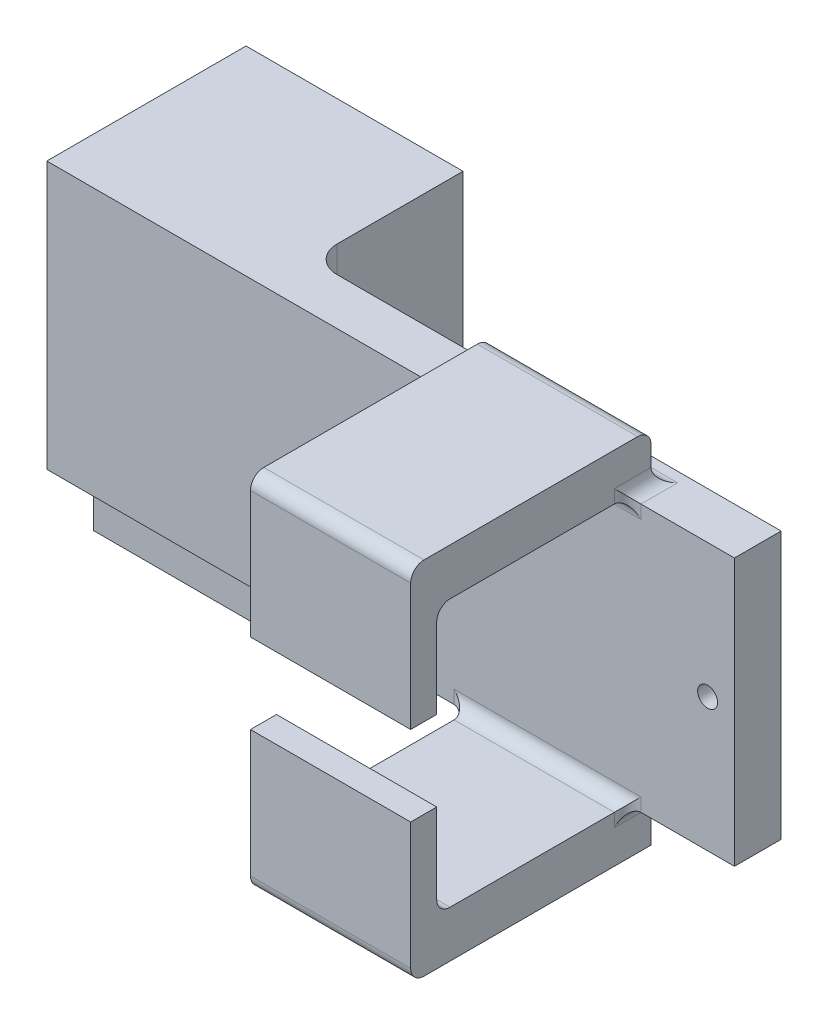
SolidWorks part; units mm, degrees
ref_plane "Front Plane" through (0, 0, 0) normal (0, 0, 1) x (1, 0, 0)
ref_plane "Top Plane" through (0, 0, 0) normal (0, 1, 0) x (1, 0, 0)
ref_plane "Right Plane" through (0, 0, 0) normal (1, 0, 0) x (0, 0, -1)
sketch "Sketch1" plane through (0, 0, 0) normal (0, 0, 1) x (1, 0, 0)
  line L1 (-25.75, 10) -> (25.75, 10)
  line L2 (-25.75, 10) -> (-25.75, -10)
  line L3 (-25.75, -10) -> (25.75, -10)
  line L4 (25.75, 10) -> (25.75, -10)
  line L5 (-25.75, 10) -> (25.75, -10) construction
  line L6 (-25.75, -10) -> (25.75, 10) construction
  point P0 (0, 0)
  dimension "D1" = 51.5
  dimension "D2" = 20
extrude "Boss-Extrude1" add sketch "Sketch1" along normal blind 3.5
sketch "Sketch2" plane through (0, 10, 0) normal (0, 1, 0) x (1, 0, 0)
  line L0 (25.75, -3.5) -> (25.75, 0) construction
  line L1 (17.75, -1.75) -> (5.75, -1.75)
  line L2 (17.75, -1.75) -> (17.75, -19.75)
  line L3 (17.75, -19.75) -> (5.75, -19.75)
  line L4 (5.75, -1.75) -> (5.75, -19.75)
  line L5 (25.75, 0) -> (-25.75, 0) construction
  dimension "D1" = 12
  dimension "D2" = 18
  dimension "D3" = 8
  dimension "D4" = 1.75
extrude "Boss-Extrude2" add sketch "Sketch2" along normal blind 3.5
fillet "Fillet1" radius 1 1 edges at (11.75, 10, 1.75)
fillet "Fillet2" radius 1 1 edges at (11.75, 10, 3.5)
sketch "Sketch3" plane through (0, -10, 0) normal (0, -1, 0) x (-1, 0, 0)
  line L0 (25.75, 0) -> (-25.75, 0) construction
  line L1 (-17.75, -1.75) -> (-5.75, -1.75)
  line L2 (-17.75, -1.75) -> (-17.75, -19.75)
  line L3 (-17.75, -19.75) -> (-5.75, -19.75)
  line L4 (-5.75, -1.75) -> (-5.75, -19.75)
  line L5 (-25.75, -3.5) -> (-25.75, 0) construction
  dimension "D1" = 12
  dimension "D2" = 1.75
  dimension "D3" = 8
  dimension "D4" = 18
extrude "Boss-Extrude3" add sketch "Sketch3" along normal blind 3.5
fillet "Fillet3" radius 1 1 edges at (11.75, -10, 1.75)
fillet "Fillet4" radius 1 1 edges at (11.75, -10, 3.5)
fillet "Fillet5" radius 1 1 edges at (17.75, 10, 2.125)
fillet "Fillet6" radius 1 1 edges at (5.75, 10, 2.125)
fillet "Fillet7" radius 1 1 edges at (17.75, 10, 3.5)
fillet "Fillet8" radius 1 1 edges at (5.75, 10, 3.5)
fillet "Fillet9" radius 1 1 edges at (5.75, -10, 2.125)
fillet "Fillet10" radius 1 1 edges at (5.75, -10, 3.5)
fillet "Fillet11" radius 1 1 edges at (17.75, -10, 2.125)
fillet "Fillet12" radius 1 1 edges at (17.75, -10, 3.5)
sketch "Sketch4" plane through (0, -10, 0) normal (0, 1, 0) x (1, 0, 0)
  line L0 (17.75, -4.5) -> (17.75, -19.75) construction
  line L1 (5.75, -19.75) -> (17.75, -19.75)
  line L2 (5.75, -19.75) -> (5.75, -17.8)
  line L3 (5.75, -17.8) -> (17.75, -17.8)
  line L4 (17.75, -19.75) -> (17.75, -17.8)
  dimension "D1" = 1.95
  dimension "D2" = 12
extrude "Boss-Extrude4" add sketch "Sketch4" along normal blind 7
sketch "Sketch5" plane through (0, 10, 0) normal (0, -1, 0) x (-1, 0, 0)
  line L0 (-17.75, -19.75) -> (-17.75, -4.5) construction
  line L1 (-5.75, -19.75) -> (-17.75, -19.75)
  line L2 (-5.75, -19.75) -> (-5.75, -17.8)
  line L3 (-5.75, -17.8) -> (-17.75, -17.8)
  line L4 (-17.75, -19.75) -> (-17.75, -17.8)
  dimension "D1" = 12
  dimension "D2" = 1.95
extrude "Boss-Extrude5" add sketch "Sketch5" along normal blind 7
fillet "Fillet13" radius 1 1 edges at (11.75, 10, 17.8)
fillet "Fillet14" radius 1 1 edges at (11.75, 13.5, 19.75)
fillet "Fillet15" radius 1 1 edges at (11.75, 13.5, 1.75)
fillet "Fillet16" radius 1 1 edges at (11.75, -13.5, 19.75)
fillet "Fillet17" radius 1 1 edges at (11.75, -10, 17.8)
sketch "Sketch8" plane through (0, 0, 0) normal (0, 0, -1) x (-1, 0, 0)
  line L7 (25.75, 10) -> (9.5, 10)
  line L8 (25.75, 10) -> (25.75, -15.7265)
  line L9 (25.75, -15.7265) -> (9.5, -15.7265)
  line L10 (9.5, 10) -> (9.5, -15.7265)
  dimension "D1" = 16.25
extrude "Boss-Extrude6" add sketch "Sketch8" along normal blind 11.42
fillet "Fillet21" radius 2 1 edges at (-9.5, 0, 0)
fillet "Fillet22" radius 2 1 edges at (-17.625, -10, 0)
fillet "Fillet23" radius 2 1 edges at (-9.5, -10, 0)
sketch "Sketch9" plane through (0, 0, 0) normal (0, 0, -1) x (-1, 0, 0)
  circle A0 centre (-23.7427, -0.005) radius 0.746
extrude "Cut-Extrude1" cut sketch "Sketch9" against normal blind 10
sketch "Sketch10" plane through (0, 0, 0) normal (0, 0, -1) x (-1, 0, 0)
  circle A3 centre (-1.39, 0) radius 0.75
extrude "Cut-Extrude2" cut sketch "Sketch10" against normal blind 10
sketch "Sketch11" plane through (0, 0, -11.42) normal (0, 0, -1) x (-1, 0, 0)
  circle A0 centre (16.5184, 3.9945) radius 1.4188
extrude "Cut-Extrude3" cut sketch "Sketch11" against normal blind 10
sketch "Sketch12" plane through (0, 0, -11.42) normal (0, 0, -1) x (-1, 0, 0)
  circle A0 centre (16.5045, -9.0002) radius 1.4018
extrude "Cut-Extrude4" cut sketch "Sketch12" against normal blind 10
